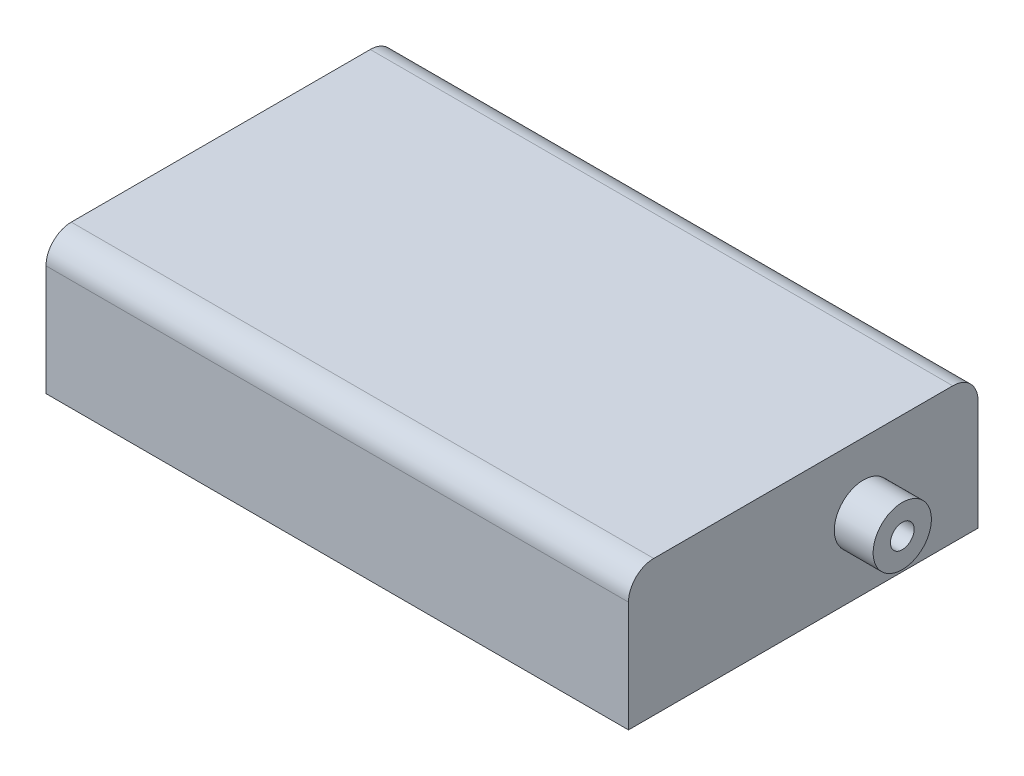
SolidWorks part; units mm, degrees
ref_plane "Front Plane" through (0, 0, 0) normal (0, 0, 1) x (1, 0, 0)
ref_plane "Top Plane" through (0, 0, 0) normal (0, 1, 0) x (1, 0, 0)
ref_plane "Right Plane" through (0, 0, 0) normal (1, 0, 0) x (0, 0, -1)
sketch "Sketch1" plane through (0, 0, 0) normal (0, 1, 0) x (1, 0, 0)
  line L1 (0, 0) -> (150, 0)
  line L2 (0, 0) -> (0, 90)
  line L3 (0, 90) -> (150, 90)
  line L4 (150, 0) -> (150, 90)
  dimension "D1" = 90
extrude "Boss-Extrude1" add sketch "Sketch1" along normal blind 35
shell "Shell2" thickness 2.5 removed face at (75, 0, -45)
sketch "Sketch5" plane through (0, 32.5, 0) normal (0, -1, 0) x (-1, 0, 0)
  line L0 (-147.5, 87.5) -> (-2.5, 87.5) construction
  line L1 (-2.5, 87.5) -> (-2.5, 2.5) construction
  line L2 (-2.5, 2.5) -> (-147.5, 2.5) construction
  line L3 (-147.5, 2.5) -> (-147.5, 87.5) construction
  circle A0 centre (-8.5, 81.5) radius 4
  circle A1 centre (-8.5, 8.5) radius 4
  circle A2 centre (-141.5, 81.5) radius 4
  circle A3 centre (-141.5, 8.5) radius 4
  dimension "D1" = 8
  dimension "D2" = 6
  dimension "D4" = 8
  dimension "D5" = 6
  dimension "D6" = 6
  dimension "D7" = 8
  dimension "D8" = 6
  dimension "D9" = 6
  dimension "D10" = 8
  dimension "D11" = 6
  dimension "D12" = 6
  dimension "D3" = 6
extrude "Boss-Extrude8" add sketch "Sketch5" along normal blind 32.5
sketch "Sketch6" plane through (0, 0, 0) normal (0, -1, 0) x (1, 0, 0)
  circle A0 centre (141.5, -81.5) radius 1.25
  circle A1 centre (141.5, -8.5) radius 1.25
  circle A2 centre (8.5, -8.5) radius 1.25
  circle A3 centre (8.5, -81.5) radius 1.25
  circle A4 centre (8.5, -81.5) radius 1.25
  circle A5 centre (8.5, -81.5) radius 4 construction
  circle A6 centre (8.5, -8.5) radius 4 construction
  circle A7 centre (141.5, -8.5) radius 4 construction
  circle A8 centre (141.5, -81.5) radius 4 construction
  dimension "D1" = 2.5
  dimension "D2" = 2.5
  dimension "D3" = 2.5
  dimension "D4" = 2.5
extrude "Cut-Extrude1" cut sketch "Sketch6" against normal blind 12 contours A3
extrude "Cut-Extrude2" cut sketch "Sketch6<3>" against normal blind 12 contours A2 | A1 | A0
sketch "Sketch6<3>" plane through (0, 0, 0) normal (0, -1, 0) x (1, 0, 0) same geometry as "Sketch6"
fillet "Fillet1" radius 6.5 1 edges at (75, 35, 0)
fillet "Fillet2" radius 6.5 1 edges at (75, 35, -90)
sketch "Sketch22" plane through (0, 32.5, 0) normal (0, -1, 0) x (1, 0, 0)
  line L0 (2.5, -87.5) -> (2.5, -2.5) construction
  line L1 (147.5, -87.5) -> (2.5, -87.5) construction
  line L2 (2.5, -87.5) -> (2.5, -2.5) construction
  circle A0 centre (82.9, -36.1) radius 3
  circle A1 centre (82.9, -9.9) radius 3
  circle A2 centre (131.1, -9.9) radius 3
  circle A3 centre (131.1, -36.1) radius 3
  circle A4 centre (82.9, -9.9) radius 1.25
  circle A5 centre (82.9, -36.1) radius 1.25
  circle A6 centre (131.1, -9.9) radius 1.25
  circle A7 centre (131.1, -36.1) radius 1.25
  dimension "D1" = 6
  dimension "D2" = 80.4
  dimension "D3" = 51.4
  dimension "D4" = 6
  dimension "D5" = 77.6
  dimension "D6" = 6
  dimension "D7" = 128.6
  dimension "D8" = 6
  dimension "D9" = 128.6
  dimension "D10" = 51.4
  dimension "D11" = 77.6
  dimension "D12" = 80.4
  dimension "D13" = 2.5
  dimension "D14" = 2.5
  dimension "D15" = 2.5
  dimension "D16" = 2.5
extrude "ESP32-screwhole" add sketch "Sketch22" along normal blind 4
sketch "Sketch25" plane through (0, 32.5, 0) normal (0, -1, 0) x (1, 0, 0)
  line L0 (2.5, -87.5) -> (2.5, -2.5) construction
  line L1 (147.5, -87.5) -> (2.5, -87.5) construction
  line L2 (147.5, -87.5) -> (2.5, -87.5) construction
  line L3 (2.5, -87.5) -> (2.5, -2.5) construction
  circle A0 centre (6, -70.5) radius 3
  circle A1 centre (6, -57.5) radius 3
  circle A2 centre (38, -57.5) radius 3
  circle A3 centre (38, -70.5) radius 3
  circle A4 centre (38, -57.5) radius 1.25
  circle A5 centre (38, -70.5) radius 1.25
  circle A6 centre (6, -57.5) radius 1.25
  circle A7 centre (6, -70.5) radius 1.25
  dimension "D1" = 6
  dimension "D2" = 3.5
  dimension "D3" = 17
  dimension "D4" = 6
  dimension "D5" = 3.5
  dimension "D6" = 30
  dimension "D7" = 6
  dimension "D8" = 35.5
  dimension "D9" = 30
  dimension "D10" = 6
  dimension "D11" = 17
  dimension "D12" = 35.5
  dimension "D13" = 2.5
  dimension "D14" = 2.5
  dimension "D15" = 2.5
  dimension "D16" = 2.5
extrude "Boss-Extrude11" add sketch "Sketch25" along normal blind 4
sketch "Sketch30" plane through (0, 32.5, 0) normal (0, -1, 0) x (1, 0, 0)
  line L0 (2.5, -52) -> (28.1, -52)
  line L1 (28.1, -32.4) -> (2.5, -32.4)
  line L2 (2.5, -32.4) -> (2.5, -30.9)
  line L3 (2.5, -30.9) -> (29.6, -30.9)
  line L4 (29.6, -30.9) -> (29.6, -53.5)
  line L5 (29.6, -53.5) -> (2.5, -53.5)
  line L6 (2.5, -53.5) -> (2.5, -52)
  line L7 (28.1, -32.4) -> (28.1, -52)
  line L8 (2.5, -87.5) -> (2.5, -2.5) construction
  line L9 (147.5, -87.5) -> (2.5, -87.5) construction
  point P10 (2.5, -52.75)
  dimension "D1" = 1.5
  dimension "D2" = 1.5
  dimension "D3" = 1.5
  dimension "D4" = 19.6
  dimension "D5" = 25.6
  dimension "D6" = 25.6
  dimension "D7" = 0
  dimension "D8" = 34
extrude "guide HW" add sketch "Sketch30" along normal blind 5
sketch "Sketch32" plane through (0, 32.5, 0) normal (0, -1, 0) x (1, 0, 0)
  line L0 (2.5, -29.4) -> (8.9, -29.4)
  line L1 (8.9, -16.2) -> (2.5, -16.2)
  line L2 (2.5, -16.2) -> (2.5, -14.7)
  line L3 (2.5, -14.7) -> (10.4, -14.7)
  line L4 (10.4, -14.7) -> (10.4, -30.9)
  line L5 (10.4, -30.9) -> (2.5, -30.9)
  line L6 (2.5, -29.4) -> (2.5, -30.9)
  line L7 (8.9, -29.4) -> (8.9, -16.2)
  line L8 (2.5, -87.5) -> (2.5, -2.5) construction
  line L9 (147.5, -87.5) -> (2.5, -87.5) construction
  dimension "D1" = 6.4
  dimension "D2" = 6.4
  dimension "D3" = 1.5
  dimension "D4" = 1.5
  dimension "D5" = 1.5
  dimension "D6" = 0
  dimension "D7" = 13.2
  dimension "D8" = 56.6
extrude "Boss-Extrude13" add sketch "Sketch32" along normal blind 16.5
sketch "Sketch33" plane through (0, 32.5, 0) normal (0, -1, 0) x (1, 0, 0)
  line L0 (2.5, -87.5) -> (2.5, -53.5) construction
  line L1 (46, -75.5) -> (69, -75.5)
  line L2 (46, -75.5) -> (46, -77.5)
  line L3 (46, -77.5) -> (69, -77.5)
  line L4 (69, -75.5) -> (69, -77.5)
  line L5 (147.5, -87.5) -> (2.5, -87.5) construction
  line L6 (147.5, -87.5) -> (2.5, -87.5) construction
  line L7 (46, -10.5) -> (69, -10.5)
  line L8 (46, -10.5) -> (46, -12.5)
  line L9 (46, -12.5) -> (69, -12.5)
  line L10 (69, -10.5) -> (69, -12.5)
  dimension "D1" = 2
  dimension "D2" = 23
  dimension "D3" = 43.5
  dimension "D4" = 10
  dimension "D5" = 2
  dimension "D6" = 75
extrude "Boss-Extrude14" add sketch "Sketch33" along normal blind 10
sketch "Sketch36" plane through (0, 0, -75.5) normal (0, 0, 1) x (1, 0, 0)
  line L0 (69, 22.5) -> (46, 22.5) construction
  line L2 (69, 22.5) -> (69, 32.5) construction
  circle A0 centre (57.5, 22.5) radius 9.5
  dimension "D1" = 19
  dimension "D4" = 11.5
extrude "Cut-Extrude8" cut sketch "Sketch36" against normal blind 2
sketch "Sketch37" plane through (0, 0, -12.5) normal (0, 0, -1) x (-1, 0, 0)
  line L0 (-46, 22.5) -> (-69, 22.5) construction
  line L2 (-46, 22.5) -> (-46, 32.5) construction
  circle A0 centre (-57.5, 22.5) radius 9.5
  dimension "D1" = 19
  dimension "D2" = 11.5
extrude "Cut-Extrude9" cut sketch "Sketch37" against normal blind 2
sketch "Sketch38" plane through (150, 0, 0) normal (1, 0, 0) x (0, 0, -1)
  line L0 (6.5, 35) -> (83.5, 35) construction
  line L1 (90, 28.5) -> (90, 0) construction
  circle A0 centre (60.5, 18) radius 7.5
  circle A1 centre (60.5, 18) radius 3.05
  dimension "D1" = 15
  dimension "D2" = 6.1
  dimension "D3" = 17
  dimension "D4" = 29.5
extrude "Boss-Extrude15" add sketch "Sketch38" along normal blind 10
sketch "Sketch40" plane through (0, 0, 0) normal (-1, 0, 0) x (0, 0, 1)
  line L0 (-90, 28.5) -> (-90, 0) construction
  line L1 (-29.4, 31.5) -> (-27.9, 31.5)
  line L2 (-29.4, 31.5) -> (-29.4, 16.5)
  line L3 (-29.4, 16.5) -> (-27.9, 16.5)
  line L4 (-27.9, 31.5) -> (-27.9, 16.5)
  line L5 (-83.5, 35) -> (-6.5, 35) construction
  line L7 (-24.9, 31.5) -> (-26.4, 31.5)
  line L8 (-24.9, 31.5) -> (-24.9, 16.5)
  line L9 (-24.9, 16.5) -> (-26.4, 16.5)
  line L10 (-26.4, 31.5) -> (-26.4, 16.5)
  line L11 (-23.4, 31.5) -> (-21.9, 31.5)
  line L12 (-23.4, 31.5) -> (-23.4, 16.5)
  line L13 (-23.4, 16.5) -> (-21.9, 16.5)
  line L14 (-21.9, 31.5) -> (-21.9, 16.5)
  line L15 (-18.9, 31.5) -> (-20.4, 31.5)
  line L16 (-18.9, 31.5) -> (-18.9, 16.5)
  line L17 (-18.9, 16.5) -> (-20.4, 16.5)
  line L18 (-20.4, 31.5) -> (-20.4, 16.5)
  line L19 (-17.4, 31.5) -> (-15.9, 31.5)
  line L20 (-17.4, 31.5) -> (-17.4, 16.5)
  line L21 (-17.4, 16.5) -> (-15.9, 16.5)
  line L22 (-15.9, 31.5) -> (-15.9, 16.5)
  dimension "D1" = 60.6
  dimension "D2" = 3.5
  dimension "D3" = 1.5
  dimension "D4" = 15
  dimension "D5" = 15
  dimension "D6" = 1.5
  dimension "D7" = 1.5
  dimension "D8" = 15
  dimension "D9" = 1.5
  dimension "D10" = 1.5
  dimension "D11" = 1.5
  dimension "D12" = 1.5
  dimension "D13" = 1.5
  dimension "D14" = 1.5
extrude "Cut-Extrude10" cut sketch "Sketch40" against normal blind 2.5
sketch "Sketch41" plane through (0, 0, 0) normal (-1, 0, 0) x (0, 0, 1)
  line L0 (-90, 28.5) -> (-90, 0) construction
  line L1 (-47.7, 30) -> (-35.7, 30)
  line L2 (-47.7, 30) -> (-47.7, 23)
  line L3 (-47.7, 23) -> (-35.7, 23)
  line L4 (-35.7, 30) -> (-35.7, 23)
  line L5 (-83.5, 35) -> (-6.5, 35) construction
  point P4 (-47.7, 26.5)
  point P7 (-41.7, 30)
  dimension "D1" = 12
  dimension "D2" = 7
  dimension "D3" = 42.3
  dimension "D4" = 5
extrude "Cut-Extrude11" cut sketch "Sketch41" against normal blind 2.5
sketch "Sketch42" plane through (0, 0, 0) normal (-1, 0, 0) x (0, 0, 1)
  line L0 (-83.5, 35) -> (-6.5, 35) construction
  line L1 (-70, 27.5) -> (-58, 27.5)
  line L2 (-70, 27.5) -> (-70, 20.5)
  line L3 (-70, 20.5) -> (-58, 20.5)
  line L4 (-58, 27.5) -> (-58, 20.5)
  line L5 (-90, 28.5) -> (-90, 0) construction
  dimension "D1" = 12
  dimension "D2" = 7
  dimension "D3" = 7.5
  dimension "D4" = 20
extrude "Cut-Extrude12" cut sketch "Sketch42" against normal blind 2.5
sketch "Sketch43" plane through (147.5, 0, 0) normal (-1, 0, 0) x (0, 0, 1)
  line L1 (-87.5, 32.5) -> (-87.5, 0) construction
  line L3 (-2.5, 32.5) -> (-87.5, 32.5) construction
  circle A0 centre (-60.5, 18) radius 8.75
  circle A1 centre (-60.5, 18) radius 10.25
  dimension "D1" = 17.5
  dimension "D2" = 14.5
  dimension "D3" = 27
  dimension "D4" = 20.5
sketch "Sketch45" plane through (0, 32.5, 0) normal (0, -1, 0) x (1, 0, 0)
  line L0 (147.5, -50.25) -> (147.5, -70.75) construction
  line L1 (85.5, -47.5) -> (87.5, -47.5)
  line L2 (85.5, -47.5) -> (85.5, -79.5)
  line L3 (85.5, -79.5) -> (87.5, -79.5)
  line L4 (87.5, -47.5) -> (87.5, -79.5)
  line L5 (147.5, -87.5) -> (2.5, -87.5) construction
  dimension "D1" = 2
  dimension "D2" = 32
  dimension "D3" = 60
  dimension "D4" = 8
extrude "Boss-Extrude16" add sketch "Sketch45" along normal blind 25
sketch "Sketch47" plane through (147.5, 0, 0) normal (-1, 0, 0) x (0, 0, 1)
  circle A0 centre (-60.5, 18) radius 3
  dimension "D1" = 6
extrude "Cut-Extrude13" cut sketch "Sketch47" against normal blind 2.5
extrude "Boss-Extrude18" add sketch "Sketch43" along normal blind 45
sketch "Sketch48" plane through (0, 0, -90) normal (0, 0, -1) x (-1, 0, 0)
  line L0 (-150, 28.5) -> (-150, 0) construction
  line L1 (-105, 21.8822) -> (-103, 21.8822)
  line L2 (-105, 21.8822) -> (-105, 6.8822)
  line L3 (-105, 6.8822) -> (-103, 6.8822)
  line L4 (-103, 21.8822) -> (-103, 6.8822)
  line L6 (-101.5, 21.8822) -> (-99.5, 21.8822)
  line L7 (-101.5, 21.8822) -> (-101.5, 6.8822)
  line L8 (-101.5, 6.8822) -> (-99.5, 6.8822)
  line L9 (-99.5, 21.8822) -> (-99.5, 6.8822)
  line L10 (-98, 21.8822) -> (-96, 21.8822)
  line L11 (-98, 21.8822) -> (-98, 6.8822)
  line L12 (-98, 6.8822) -> (-96, 6.8822)
  line L13 (-96, 21.8822) -> (-96, 6.8822)
  line L14 (-92.5, 21.8822) -> (-94.5, 21.8822)
  line L15 (-92.5, 21.8822) -> (-92.5, 6.8822)
  line L16 (-92.5, 6.8822) -> (-94.5, 6.8822)
  line L17 (-94.5, 21.8822) -> (-94.5, 6.8822)
  line L18 (-91, 21.8822) -> (-89, 21.8822)
  line L19 (-91, 21.8822) -> (-91, 6.8822)
  line L20 (-91, 6.8822) -> (-89, 6.8822)
  line L21 (-89, 21.8822) -> (-89, 6.8822)
  line L22 (-87.5, 21.8822) -> (-85.5, 21.8822)
  line L23 (-87.5, 21.8822) -> (-87.5, 6.8822)
  line L24 (-87.5, 6.8822) -> (-85.5, 6.8822)
  line L25 (-85.5, 21.8822) -> (-85.5, 6.8822)
  point P14 (-100.5, 21.8822)
  dimension "D1" = 2
  dimension "D2" = 15
  dimension "D3" = 45
  dimension "D4" = 15
  dimension "D5" = 2
  dimension "D6" = 1.5
  dimension "D7" = 2
  dimension "D8" = 15
  dimension "D9" = 0
  dimension "D10" = 1.5
  dimension "D11" = 2
  dimension "D12" = 15
  dimension "D13" = 1.5
  dimension "D14" = 2
  dimension "D15" = 1.5
  dimension "D16" = 15
  dimension "D17" = 2
  dimension "D18" = 1.5
